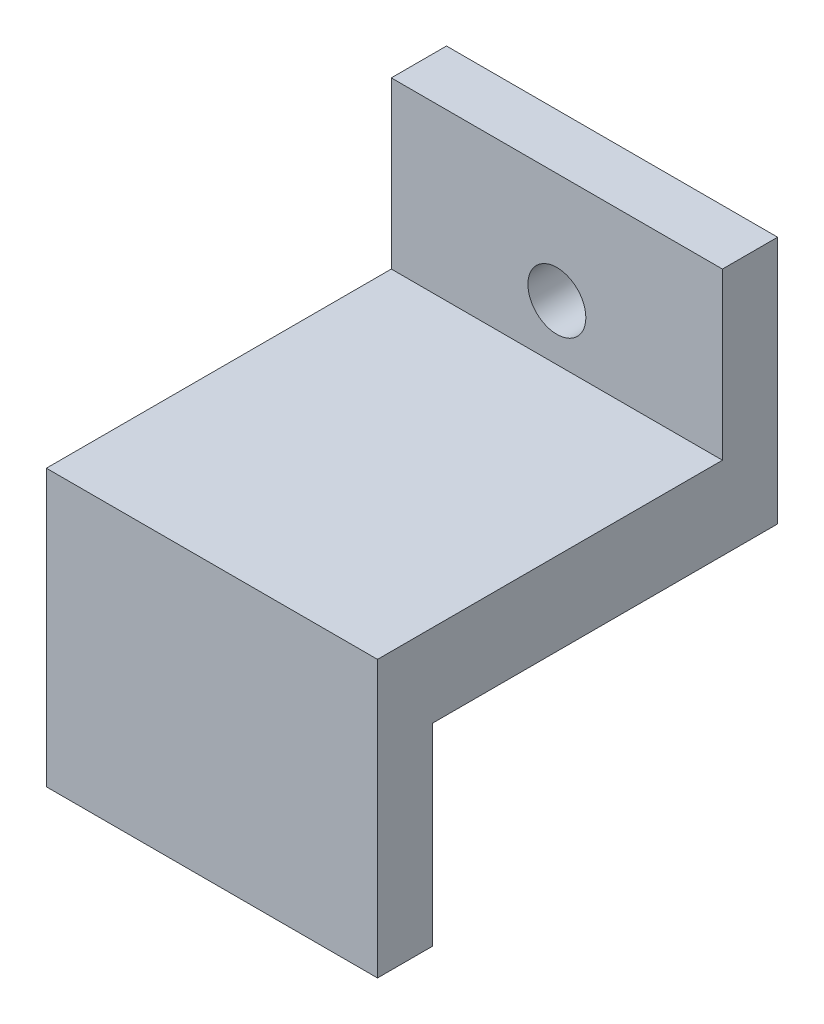
SolidWorks part; units mm, degrees
ref_plane "Front Plane" through (0, 0, 0) normal (0, 0, 1) x (1, 0, 0)
ref_plane "Top Plane" through (0, 0, 0) normal (0, 1, 0) x (1, 0, 0)
ref_plane "Right Plane" through (0, 0, 0) normal (1, 0, 0) x (0, 0, -1)
sketch "Sketch1" plane through (0, 0, 0) normal (0, 0, 1) x (1, 0, 0)
  line L1 (-26, 31) -> (-14, 31)
  line L2 (-26, 31) -> (-26, 40)
  line L3 (-26, 40) -> (-14, 40)
  line L4 (-14, 31) -> (-14, 40)
  circle A0 centre (-20, 36) radius 1.05
extrude "Link_Eye_Shelf" add sketch "Sketch1" along normal blind 2 from offset 14.5 offset against normal yes
sketch "Sketch2" plane through (0, 0, 0) normal (0, 0, 1) x (1, 0, 0)
  line L1 (-26, 31) -> (-14, 31)
  line L2 (-26, 31) -> (-26, 34)
  line L3 (-26, 34) -> (-14, 34)
  line L4 (-14, 31) -> (-14, 34)
extrude "Outboard_Web" add sketch "Sketch2" along normal blind 12.5 from offset 13.5 offset against normal yes
sketch "Sketch3" plane through (0, 0, 0) normal (0, 0, 1) x (1, 0, 0)
  line L1 (-26, 24) -> (-14, 24)
  line L2 (-26, 24) -> (-26, 34)
  line L3 (-26, 34) -> (-14, 34)
  line L4 (-14, 24) -> (-14, 34)
extrude "Intermediate_Plate_Foot" add sketch "Sketch3" along normal blind 2 from offset 2 offset against normal yes
